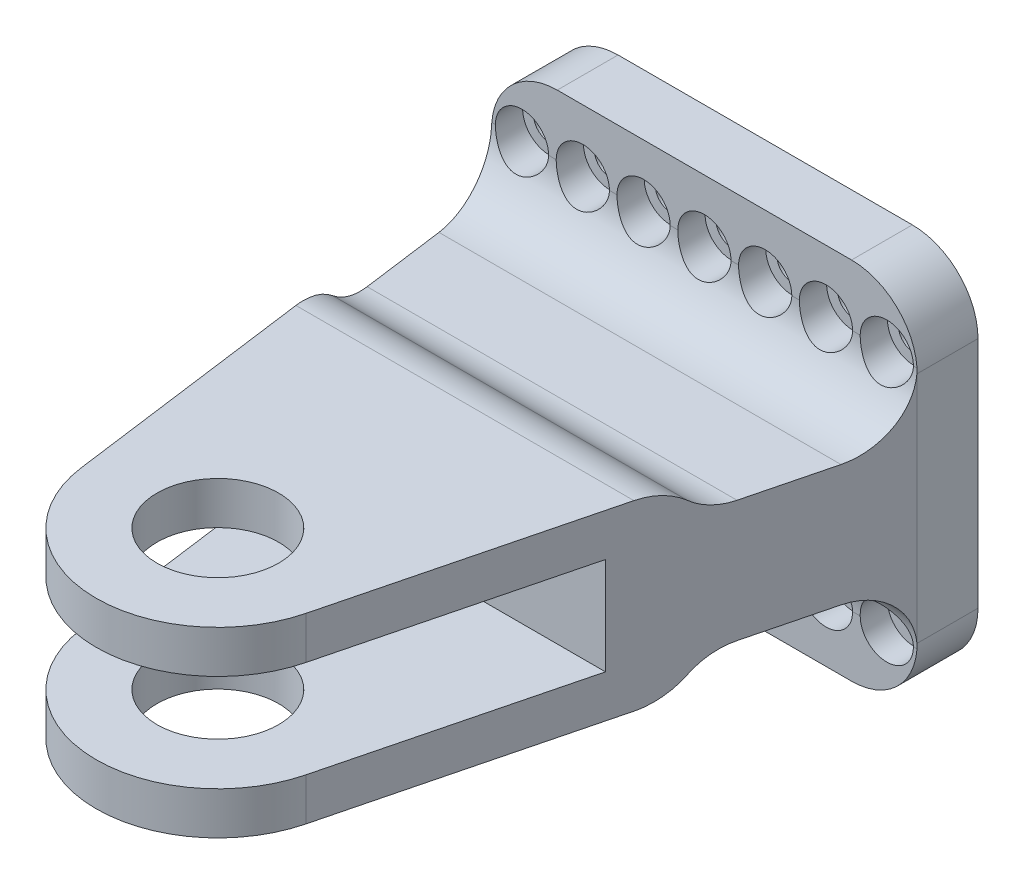
SolidWorks part; units mm, degrees
material "Water"
ref_plane "XY" through (0, 0, 0) normal (0, 0, 1) x (1, 0, 0)
ref_plane "XZ" through (0, 0, 0) normal (0, 1, 0) x (1, 0, 0)
ref_plane "YZ" through (0, 0, 0) normal (1, 0, 0) x (0, 0, -1)
ref_axis "X" through (-24.4475, 0, 0) along (1, 0, 0)
ref_axis "Y" through (0, -20.955, 0) along (0, 1, 0)
ref_axis "Z" through (0, 0, 66.8777) along (0, 0, -1)
sketch "Sketch1" plane through (0, 0, 0) normal (0, 0, 1) x (1, 0, 0)
  line L1 (-22.225, -19.05) -> (22.225, -19.05)
  line L2 (-22.225, -19.05) -> (-22.225, 19.05)
  line L3 (-22.225, 19.05) -> (22.225, 19.05)
  line L4 (22.225, -19.05) -> (22.225, 19.05)
  line L5 (-22.225, -19.05) -> (22.225, 19.05) construction
  line L6 (-22.225, 19.05) -> (22.225, -19.05) construction
  point P0 (0, 0)
  dimension "D1" = 38.1
  dimension "D2" = 44.45
extrude "Boss-Extrude1" add sketch "Sketch1" along normal blind 6.35
hole_wizard "CBORE for #4 Socket Head Cap Screw1" positions "Sketch2" profile "Sketch3" counterbore size "#4" standard "ANSI Inch" end condition up to next
sketch "Sketch2" plane through (0, 0, 6.35) normal (0, 0, 1) x (1, 0, 0)
  line L1 (-19.05, 12.7) -> (19.05, 12.7)
  line L2 (-19.05, 12.7) -> (-19.05, -12.7)
  line L3 (-19.05, -12.7) -> (19.05, -12.7)
  line L4 (19.05, 12.7) -> (19.05, -12.7)
  line L5 (0, -12.7) -> (0, 12.7) construction
  point P0 (-19.05, 12.7)
  point P5 (19.05, -12.7)
  point P108 (-19.05, -12.7)
  point P109 (19.05, 12.7)
  point P122 (12.7, -12.7)
  point P123 (12.7, 12.7)
  point P124 (6.35, -12.7)
  point P125 (6.35, 12.7)
  point P126 (0, -12.7)
  point P127 (0, 12.7)
  point P128 (-6.35, -12.7)
  point P129 (-6.35, 12.7)
  point P130 (-12.7, -12.7)
  point P131 (-12.7, 12.7)
  dimension "D1" = 25.4
  dimension "D2" = 38.1
  dimension "D3" = 6
sketch "Sketch3" plane through (-19.05, 12.7, 6.35) normal (1, 0, 0) x (0, -1, 0)
  line L0 (0, 0) -> (0, 6.35)
  line L1 (0, 6.35) -> (1.6319, 6.35)
  line L3 (1.6319, 6.35) -> (1.6319, 2.8448)
  line L4 (1.6319, 2.8448) -> (2.7788, 2.8448)
  line L5 (2.7788, 2.8448) -> (2.7788, 0)
  line L7 (2.7788, 0) -> (0, 0)
  line L11 (0, -6.35) -> (0, 107.95) construction
  dimension "Thru Hole Dia." = 3.2639
  dimension "Thru Hole Depth" = 6.35
  dimension "C'Bore Dia." = 5.5575
  dimension "C'Bore Depth" = 2.8448
sketch "Sketch4" plane through (0, 0, 0) normal (0, 1, 0) x (1, 0, 0)
  line L0 (0, 0) -> (-3, -54.168) construction
  line L1 (-15.5874, -55.8557) -> (-22.225, -6.35)
  line L2 (-22.225, -6.35) -> (22.225, -6.35) construction
  line L3 (9.3105, -57.2891) -> (22.225, -6.35)
  line L4 (-22.225, -6.35) -> (22.225, -6.35)
  line L5 (22.225, 0) -> (-22.225, 0) construction
  circle A0 centre (-3, -54.168) radius 12.7 construction
  circle A1 centre (-3, -54.168) radius 6.35
  arc A2 (-15.5874, -55.8557) -> (9.3105, -57.2891) centre (-3, -54.168) ccw
  dimension "D1" = 25.4
  dimension "D3" = 12.7
  dimension "D4" = 25.4
  dimension "D2" = 54.168
  dimension "D5" = 3
extrude "Boss-Extrude2" add sketch "Sketch4" along normal mid plane 12.7
sketch "Sketch5" plane through (0, 0, 0) normal (0, 1, 0) x (1, 0, 0)
  line L0 (17.0244, -26.863) -> (-19.4747, -26.863)
  line L3 (9.3105, -57.2891) -> (22.225, -6.35)
  line L4 (22.225, -6.35) -> (-22.225, -6.35)
  line L5 (-22.225, -6.35) -> (-15.5874, -55.8557)
  line L6 (9.3105, -57.2891) -> (17.0244, -26.863)
  line L8 (-19.4747, -26.863) -> (-15.5874, -55.8557)
  circle A0 centre (-3, -54.168) radius 6.35 construction
  arc A1 (-15.5874, -55.8557) -> (9.3105, -57.2891) centre (-3, -54.168) ccw
  arc A2 (-15.5874, -55.8557) -> (9.3105, -57.2891) centre (-3, -54.168) ccw
  circle A3 centre (-3, -54.168) radius 6.35
  dimension "D2" = 27.305
  dimension "D1" = 0
extrude "Boss-Extrude3" add sketch "Sketch5" along normal mid plane 19.05
sketch "Sketch6" plane through (0, 0, 0) normal (0, 1, 0) x (1, 0, 0)
  line L0 (-18.7425, -32.324) -> (15.6399, -32.324)
  line L3 (-19.4747, -26.863) -> (-15.5874, -55.8557)
  line L4 (17.0244, -26.863) -> (-19.4747, -26.863)
  line L5 (9.3105, -57.2891) -> (17.0244, -26.863)
  line L6 (-18.7425, -32.324) -> (-15.5874, -55.8557)
  line L8 (9.3105, -57.2891) -> (15.6399, -32.324)
  arc A1 (-15.5874, -55.8557) -> (9.3105, -57.2891) centre (-3, -54.168) ccw
  arc A2 (-15.5874, -55.8557) -> (9.3105, -57.2891) centre (-3, -54.168) ccw
  dimension "D2" = 21.844
  dimension "D1" = 0
extrude "Cut-Extrude1" cut sketch "Sketch6" against normal mid plane 10.16
fillet "Fillet3" radius 6.35 4 edges at (0, 6.35, 6.35) (0, -6.35, 6.35) (-1.2251, -6.35, 26.863) (-1.2251, 6.35, 26.863)
fillet "Fillet2" radius 6.858 6 edges at (-22.225, 19.05, 3.175) (-22.225, -19.05, 3.175) (22.225, -19.05, 3.175) (22.225, 19.05, 3.175) (-1.2251, 9.525, 26.863) (-1.2251, -9.525, 26.863)
